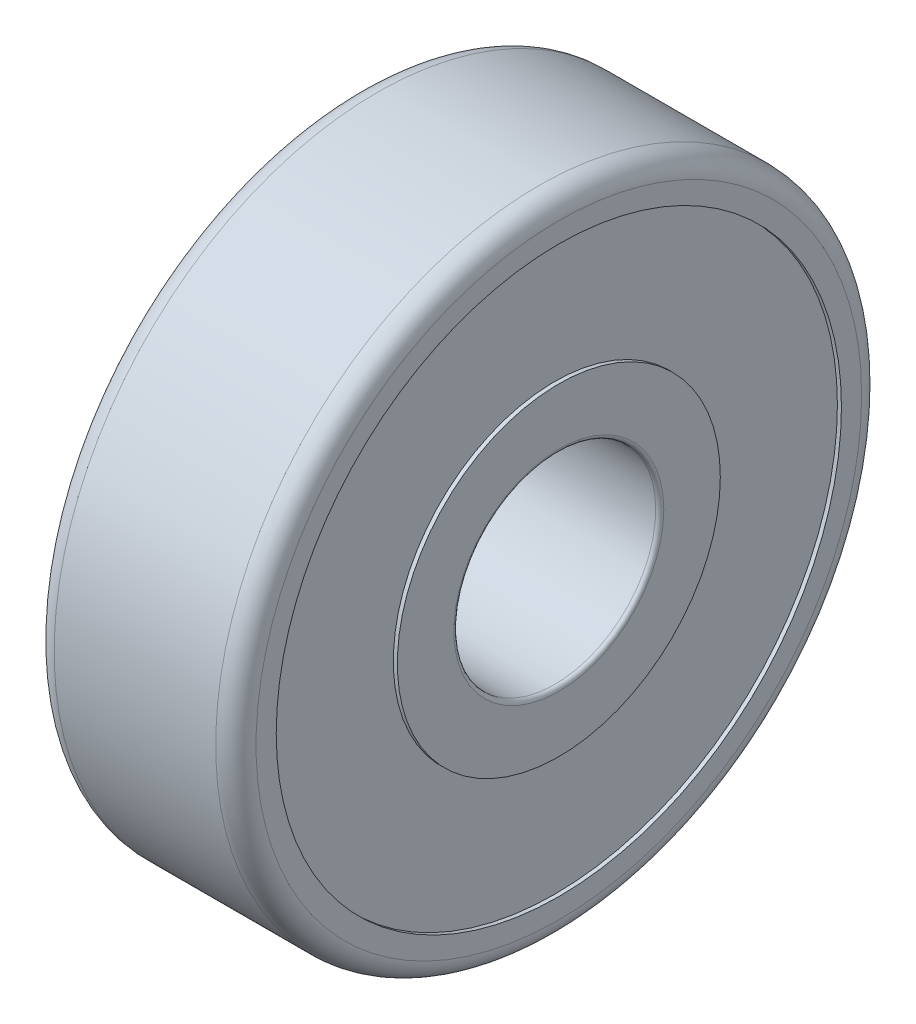
SolidWorks part; units mm, degrees
material "1.4000 (X6Cr13)"
ref_plane "Alzado" through (0, 0, 0) normal (0, 0, 1) x (1, 0, 0)
ref_plane "Planta" through (0, 0, 0) normal (0, 1, 0) x (1, 0, 0)
ref_plane "Vista lateral" through (0, 0, 0) normal (1, 0, 0) x (0, 0, -1)
sketch "Croquis2" plane through (0, 0, 0) normal (1, 0, 0) x (0, 0, -1)
  circle A0 centre (0, 0) radius 2.5
  circle A1 centre (0, 0) radius 8
extrude "Saliente-Extruir2" add sketch "Croquis2" along normal blind 2.5 and the other way blind 2.5
fillet "Redondeo1" radius 0.5 2 edges at (2.5, 0, -8) (-2.5, 0, -8)
fillet "Redondeo2" radius 0.1 2 edges at (-2.5, 0, -2.5) (2.5, 0, -2.5)
sketch "Croquis3" plane through (-2.5, 0, 0) normal (-1, 0, 0) x (0, 0, 1)
  circle A0 centre (0, 0) radius 4
  circle A1 centre (0, 0) radius 7
  dimension "D1" = 14
  dimension "D2" = 8
ref_plane "Plano2" through (2.5, 0, 0) normal (1, 0, 0) x (0, 0, -1)
sketch "Croquis4" plane through (2.5, 0, 0) normal (1, 0, 0) x (0, 0, -1)
  circle A0 centre (0, 0) radius 4
  circle A1 centre (0, 0) radius 7
  dimension "D1" = 14
  dimension "D2" = 8
extrude "Cortar-Extruir1" cut sketch "Croquis3" against normal blind 0.1
extrude "Cortar-Extruir2" cut sketch "Croquis4" against normal blind 0.1
